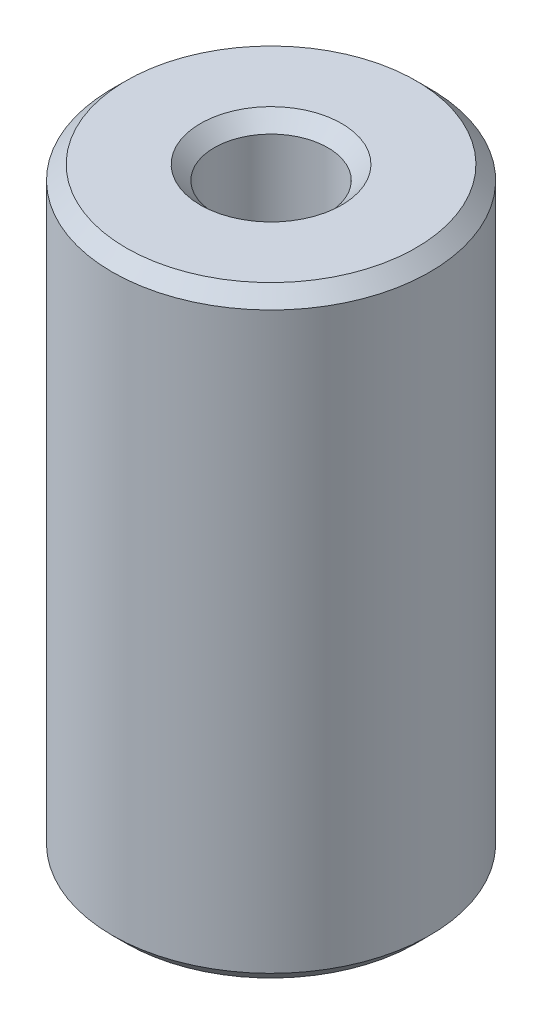
SolidWorks part; units mm, degrees
ref_plane "Front Plane" through (0, 0, 0) normal (0, 0, 1) x (1, 0, 0)
ref_plane "Top Plane" through (0, 0, 0) normal (0, 1, 0) x (1, 0, 0)
ref_plane "Right Plane" through (0, 0, 0) normal (1, 0, 0) x (0, 0, -1)
sketch "Sketch1" plane through (0, 0, 0) normal (0, 1, 0) x (1, 0, 0)
  circle A0 centre (0, 0) radius 7.5
  dimension "SLEEVE_OD" = 15
extrude "Boss-Extrude1" add sketch "Sketch1" along normal blind 28.4437
sketch "Sketch2" plane through (0, 0, 0) normal (0, 1, 0) x (1, 0, 0)
  circle A0 centre (0, 0) radius 2.6796
  dimension "BORE_D" = 5.3592
extrude "Cut-Extrude1" cut sketch "Sketch2" along normal through all
chamfer "Chamfer1" distance 0.6576 angle 45 4 edges at (0, 28.4437, 2.6796) (0, 0, 2.6796) (0, 0, 7.5) (0, 28.4437, 7.5)
